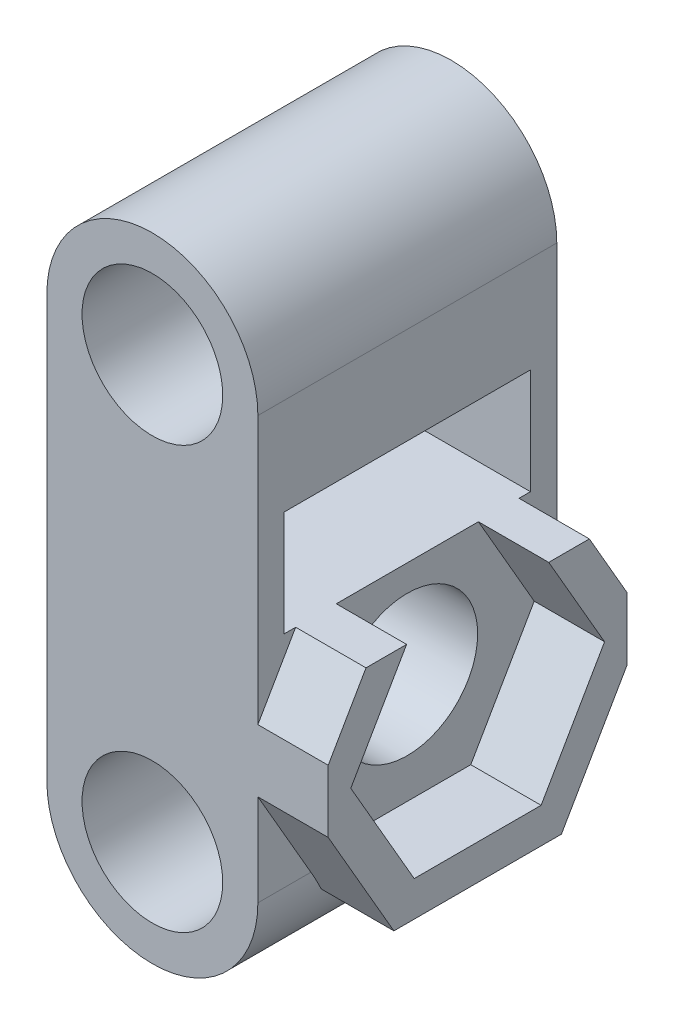
SolidWorks part; units mm, degrees
ref_plane "Front Plane" through (0, 0, 0) normal (0, 0, 1) x (1, 0, 0)
ref_plane "Top Plane" through (0, 0, 0) normal (0, 1, 0) x (1, 0, 0)
ref_plane "Right Plane" through (0, 0, 0) normal (1, 0, 0) x (0, 0, -1)
sketch "Sketch1" plane through (0, 0, 0) normal (0, 0, 1) x (1, 0, 0)
  line L0 (0, 0) -> (0, -12) construction
  line L1 (-3, 0) -> (-3, -12)
  line L2 (3, 0) -> (3, -12)
  arc A0 (3, 0) -> (-3, 0) centre (0, 0) ccw
  arc A1 (-3, -12) -> (3, -12) centre (0, -12) ccw
  circle A2 centre (0, 0) radius 2
  circle A3 centre (0, -12) radius 2
  dimension "D2" = 6
  dimension "D6" = 4
  dimension "D7" = 4
  dimension "D1" = 12
extrude "Boss-Extrude1" add sketch "Sketch1" along normal blind 8.5
sketch "Sketch2" plane through (3, 0, 0) normal (1, 0, 0) x (0, 0, -1)
  line L0 (-8.5, -6) -> (0, -6) construction
  line L1 (-8.5, -12) -> (-8.5, 0) construction
  line L2 (0, -12) -> (0, 0) construction
  line L3 (-4.25, 0) -> (-4.25, -12) construction
  line L4 (-8.5, 0) -> (0, 0) construction
  line L5 (-8.5, -12) -> (0, -12) construction
  circle A0 centre (-4.25, -8.5) radius 2
  dimension "D1" = 4
  dimension "D2" = 2.5
extrude "Cut-Extrude1" cut sketch "Sketch2" against normal through all
sketch "Sketch3" plane through (3, 0, 0) normal (1, 0, 0) x (0, 0, -1)
  line L1 (-0.6416, -8.5) -> (-2.4458, -5.375)
  line L2 (-2.4458, -5.375) -> (-6.0542, -5.375)
  line L3 (-6.0542, -5.375) -> (-7.8584, -8.5)
  line L4 (-7.8584, -8.5) -> (-6.0542, -11.625)
  line L5 (-6.0542, -11.625) -> (-2.4458, -11.625)
  line L6 (-2.4458, -11.625) -> (-0.6416, -8.5)
  line L7 (-1.8684, -4.375) -> (-6.6316, -4.375)
  line L8 (-6.6316, -4.375) -> (-9.0131, -8.5)
  line L9 (-9.0131, -8.5) -> (-6.6316, -12.625)
  line L10 (-6.6316, -12.625) -> (-1.8684, -12.625)
  line L11 (-1.8684, -12.625) -> (0.5131, -8.5)
  line L12 (0.5131, -8.5) -> (-1.8684, -4.375)
  circle A0 centre (-4.25, -8.5) radius 3.125 construction
  circle A1 centre (-4.25, -8.5) radius 4.125 construction
  dimension "D1" = 6.25
  dimension "D2" = 1
extrude "Boss-Extrude2" add sketch "Sketch3" along normal blind 2 and the other way blind 0.5
sketch "Sketch4" plane through (-3, 0, 0) normal (-1, 0, 0) x (0, 0, 1)
  line L0 (4.25, 0) -> (4.25, -6.5) construction
  line L1 (8.5, 0) -> (0, 0) construction
  line L3 (0.75, -2.75) -> (7.75, -2.75)
  line L4 (0.75, -2.75) -> (0.75, -5.75)
  line L5 (0.75, -5.75) -> (7.75, -5.75)
  line L6 (7.75, -2.75) -> (7.75, -5.75)
  line L7 (0.75, -2.75) -> (7.75, -5.75) construction
  line L8 (0.75, -5.75) -> (7.75, -2.75) construction
  circle A0 centre (4.25, -8.5) radius 2 construction
  point P7 (4.25, -4.25)
  dimension "D1" = 7
  dimension "D2" = 3
  dimension "D3" = 2.75
extrude "Cut-Extrude2" cut sketch "Sketch4" against normal through all
sketch "Sketch5" plane through (-3, 0, 0) normal (-1, 0, 0) x (0, 0, 1)
  line L0 (4.25, 0) -> (4.25, -12) construction
  line L1 (8.5, 0) -> (0, 0) construction
  line L2 (8.5, -12) -> (0, -12) construction
  line L3 (0, -6) -> (8.5, -6) construction
  line L4 (0, 0) -> (0, -12) construction
  line L5 (8.5, 0) -> (8.5, -12) construction
  line L7 (0, -15) -> (8.5, -15)
  line L8 (0, -15) -> (0, 3)
  line L9 (0, 3) -> (8.5, 3)
  line L10 (8.5, -15) -> (8.5, 3)
  line L11 (0, -15) -> (8.5, 3) construction
  line L12 (0, 3) -> (8.5, -15) construction
  point P12 (4.25, -6)
extrude "Cut-Extrude3" cut sketch "Sketch5" against normal through all flip side to cut
equation "\"X-ROD-SPACING\"=45"
equation "\"Y-ROD-SPACING\"=75"
equation "\"Z-ROD-SPACING\"=17.5"
equation "\"Y-BED-OFFSET\"=2"
equation "\"Y-BED-ROD-INSET\"=3.5"
equation "\"Y-BED-SCREW-SPACING\"=209"
equation "\"Y-BED-SCREW-CUTOUT-SLOT-HEIGHT\"=2"
equation "\"T-SLOT-NUT-FILLET-RADIUS\"=0.25"
equation "\"T-SLOT-SCREW-SHAFT-RADIUS\"=1.75"
equation "\"T-SLOT-SCREW-SHAFT-CUTOUT-LENGTH\"=10.5"
equation "\"T-SLOT-NUT-DEPTH\"=4.2"
equation "\"T-SLOT-NUT-WIDTH\"=3"
equation "\"T-SLOT-NUT-END-DISTANCE\"=8"
equation "\"ACRYLIC-THICKNESS\"=10"
equation "\"ACRYLIC-THICKNESS2\"=4.5"
equation "\"ACRYLIC-TAB-CUTOUT-SIZE\"=\"ACRYLIC-THICKNESS\"+\"ACRYLIC-TAB-TOLERANCE\"*2"
equation "\"ACRYLIC-TAB-TOLERANCE\"=.1"
equation "\"ACRYLIC-TAB-WIDTH\"=\"ACRYLIC-THICKNESS\""
equation "\"ACRYLIC-M3-HOLE\"=3.1"
equation "\"SMOOTHROD-CAP-SCREW-DISTANCE\"=20"
equation "\"FRAME-WIDTH-INNER\"=370"
equation "\"NEMA17-HOLE-SPACING\"=31"
equation "\"NEMA17-CENTRAL-CUTOUT\"=22.5"
equation "\"Z-BRACKET-REACH\"=55"
equation "\"Z-ROD-INSET\"=16"
equation "\"TOP-BRACKET-SPACING\"=40"
equation "\"SMOOTHROD-X-LENGTH\"=350"
equation "\"SMOOTHROD-Y-LENGTH\"=350"
equation "\"SMOOTHROD-Z-LENGTH\"=350"
equation "\"SMOOTHROD-TIGHTENING-HEADROOM\"=.25"
equation "\"LEADSCREW-Z-LENGTH\"=300"
equation "\"SCREW-LENGTH-FRAME\"=\"ACRYLIC-THICKNESS\" + 10"
equation "\"SCREW-LENGTH-MOTOR\"=\"ACRYLIC-THICKNESS\" + 5"
equation "\"SCREW-LENGTH-EXTRUDER\"=28"
equation "\"SCREW-HEAD-RADIUS\"=6"
equation "\"PRINTED-M3-HOLE\"=3.5"
equation "\"PRINTED-X-SMOOTHROD-DIAMETER\"=8.2"
equation "\"PRINTED-X-SMOOTHROD-CUTOUT\"=10"
equation "\"PRINTED-X-BASE-HEIGHT\"=10"
equation "\"PRINTED-LM8UU-CUTOUT-SIZE\"=15.25"
equation "\"PRINTED-LM8UU-CUTOUT-LENGTH\"=24.5"
equation "\"PRINTED-X-IDLER-HEIGHT\"=16"
equation "\"PRINTED-M3-NUT-AF\"=6.25"
equation "\"PSU-MOUNTING-WIDTH\"=95"
equation "\"PSU-MOUNTING-HEIGHT\"=177"
equation "\"Y-BELT-TO-ROD-DISTANCE\"=20"
equation "\"SPOOL-HOLDER-ROD-SPACING\"=150"
equation "\"ACRYLIC-X-CARRIAGE-WIDTH\"=55"
equation "\"ACRYLIC-X-CARRIAGE-HEIGHT\"=75"
equation "\"ACRYLIC-X-CARRIAGE-LM8UU-CUTOUT-WIDTH\"=24.25"
equation "\"ACRYLIC-X-CARRIAGE-LM8UU-CUTOUT-HEIGHT\"=11.5"
equation "\"ACRYLIC-X-CARRIAGE-SCREW-SPACING-X\"=15"
equation "\"ACRYLIC-X-CARRIAGE-SCREW-SPACING-Y\"=33"
equation "\"ACRYLIC-X-CARRIAGE-CENTER-TAB-SPACING\"=14"
equation "\"ACRYLIC-X-CARRIAGE-EXTRUDER-OFFSET\"=26"
equation "\"ACRYLIC-X-CARRIAGE-EXTRUDER-ANGLE\"=90"
equation "\"ACRYLIC-X-CARRIAGE-EXTRUDER-SHELF-DEPTH\"=\"ACRYLIC-X-CARRIAGE-EXTRUDER-OFFSET\" + 28"
equation "\"ACRYLIC-X-CARRIAGE-EXTRUDER-BRACE-SPACING\"=23"
equation "\"ACRYLIC-X-CARRIAGE-EXTRUDER-BRACE-TAB-OFFSET\"=20"
equation "\"ACRYLIC-X-CARRIAGE-EXTRUDER-BRACE-HEIGHT\"=35"
equation "\"ACRYLIC-X-CARRIAGE-EXTRUDER-BRACE-SCREW-SPACING\"=22"
equation "\"ACRYLIC-X-CARRIAGE-DUAL-WIDTH-MULTIPLIER\"=1.65"
equation "\"ACRYLIC-X-CARRIAGE-DUAL-HOTEND-SPACING\"=42"
equation "\"ACRYLIC-X-CARRIAGE-DUAL-WIDTH\"=103"
equation "\"ACRYLIC-X-CARRIAGE-DUAL-HOTEND-SEPARATION\"=35"
equation "\"ACRYLIC-X-CARRIAGE-DUAL-MOUNT-PLATE-DEPTH\"=76"
equation "\"ACRYLIC-X-CARRIAGE-DUAL-MOUNT-BRACE-WIDTH\"=45"
equation "\"ACRYLIC-X-CARRIAGE-DUAL-MOUNT-SCREW-WIDTH\"=40"
equation "\"BLOWER-FAN-WIDTH\"=15"
equation "\"D1@Sketch3\"=\"PRINTED-M3-NUT-AF\""
